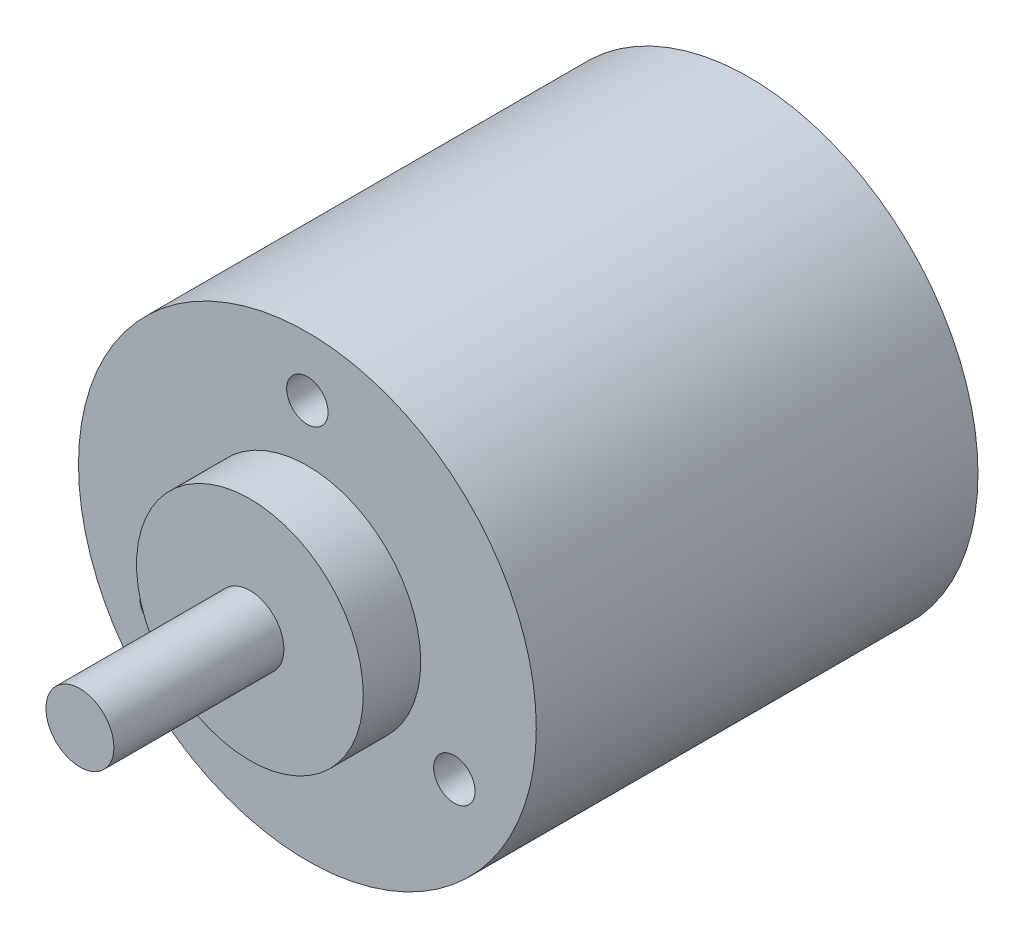
SolidWorks part; units mm, degrees
ref_plane "Front Plane" through (0, 0, 0) normal (0, 0, 1) x (1, 0, 0)
ref_plane "Top Plane" through (0, 0, 0) normal (0, 1, 0) x (1, 0, 0)
ref_plane "Right Plane" through (0, 0, 0) normal (1, 0, 0) x (0, 0, -1)
sketch "Sketch1" plane through (0, 0, 0) normal (0, 0, 1) x (1, 0, 0)
  circle A0 centre (0, 0) radius 20.2311
  dimension "D1" = 40.4622
extrude "Boss-Extrude1" add sketch "Sketch1" along normal mid plane 39.0398
sketch "Sketch2" plane through (0, 0, 19.5199) normal (0, 0, 1) x (1, 0, 0)
  circle A0 centre (0, 0) radius 10.0203
  dimension "D1" = 20.0406
extrude "Boss-Extrude2" add sketch "Sketch2" along normal blind 5.08
sketch "Sketch3" plane through (0, 0, 24.5999) normal (0, 0, 1) x (1, 0, 0)
  circle A0 centre (0, 0) radius 3.0035
  dimension "D1" = 6.0071
extrude "Boss-Extrude3" add sketch "Sketch3" along normal blind 15.0241
sketch "Sketch4" plane through (0, 0, 19.5199) normal (0, 0, 1) x (1, 0, 0)
  circle A0 centre (0, 0) radius 15 construction
  circle A1 centre (0, 15) radius 1.8288
  circle A2 centre (12.9904, -7.5) radius 1.8288
  circle A3 centre (-12.9904, -7.5) radius 1.8288
  point P11 (0, 0)
  dimension "D1" = 30
  dimension "D2" = 3.6576
  dimension "D3" = 3
extrude "Cut-Extrude1" cut sketch "Sketch4" against normal blind 7
